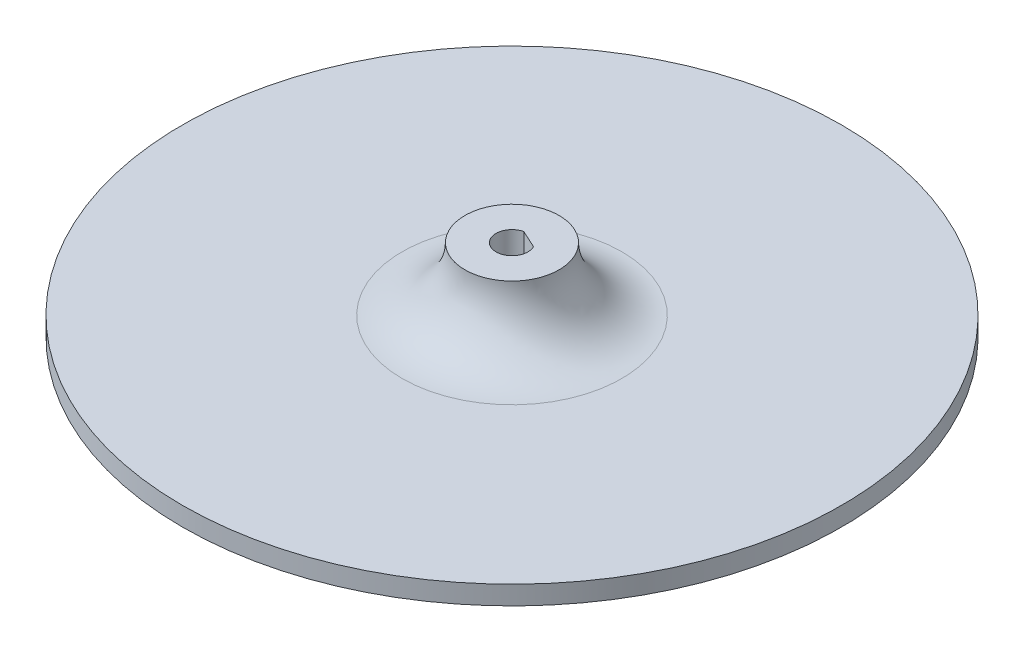
SolidWorks part; units mm, degrees
ref_plane "Ebene vorne" through (0, 0, 0) normal (0, 0, 1) x (1, 0, 0)
ref_plane "Ebene oben" through (0, 0, 0) normal (0, 1, 0) x (1, 0, 0)
ref_plane "Ebene rechts" through (0, 0, 0) normal (1, 0, 0) x (0, 0, -1)
sketch "Skizze1" plane through (0, 0, 0) normal (0, 1, 0) x (1, 0, 0)
  line L0 (-0.6015, 2.478) -> (2.2729, 1.156)
  circle A0 centre (0, 0) radius 52.5
  circle A1 centre (0, 0) radius 2.55
  circle A3 centre (0, 0) radius 7.5
  dimension "D1" = 105
  dimension "D3" = 5.1
  dimension "D4" = 15
  dimension "D2" = 3.1639
extrude "Aufsatz-Linear austragen1" add sketch "Skizze1" against normal blind 3 contours A3 A1 | L0 A1 | L0 A1 | A0 A3 region at (0.9285, 0, -2.0189) region at (-0.0573, 0, 0.1246) region at (-51.0151, 0, 0) region at (-7.2879, 0, 0)
extrude "Aufsatz-Linear austragen2" add sketch "Skizze1<3>" along normal blind 10 contours L0 A1 | A3 A1 region at (0.9285, 0, -2.0189) region at (-7.2879, 0, 0)
sketch "Skizze1<3>" plane through (0, 0, 0) normal (0, 1, 0) x (1, 0, 0) same geometry as "Skizze1"
fillet "Verrundung1" radius 10 1 edges at (0, 0, 7.5)
